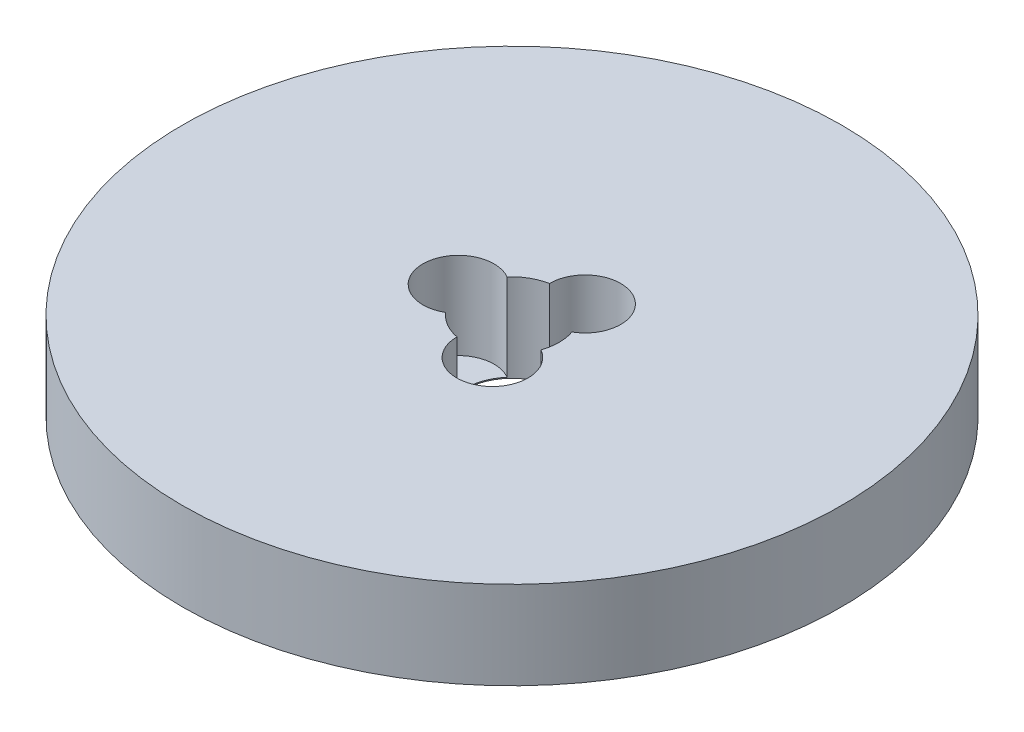
SolidWorks part; units mm, degrees
ref_plane "Front Plane" through (0, 0, 0) normal (0, 0, 1) x (1, 0, 0)
ref_plane "Top Plane" through (0, 0, 0) normal (0, 1, 0) x (1, 0, 0)
ref_plane "Right Plane" through (0, 0, 0) normal (1, 0, 0) x (0, 0, -1)
sketch "Sketch1" plane through (0, 0, 0) normal (0, 1, 0) x (1, 0, 0)
  circle A0 centre (0, 0) radius 52.5
  dimension "FLANGE_OD" = 105
extrude "Boss-Extrude1" add sketch "Sketch1" along normal blind 14
sketch "Sketch2" plane through (0, 0, 0) normal (0, 1, 0) x (1, 0, 0)
  circle A0 centre (0, 0) radius 7.5
  dimension "BORE_D" = 15
extrude "Cut-Extrude1" cut sketch "Sketch2" along normal through all
sketch "Sketch3" plane through (0, 14, 0) normal (0, 1, 0) x (1, 0, 0)
  circle A0 centre (0, 0) radius 8.5284 construction
  circle A1 centre (-8.5284, 0) radius 5.6684
  dimension "BOLT_D" = 11.3368
  dimension "BOLT_PCD" = 17.0568
extrude "Cut-Extrude2" cut sketch "Sketch3" against normal blind 13.8377
pattern_circular "CirPattern1" count 3 over 360 about axis through (0, 0, 0) along (0, 1, 0) of "Cut-Extrude2"
